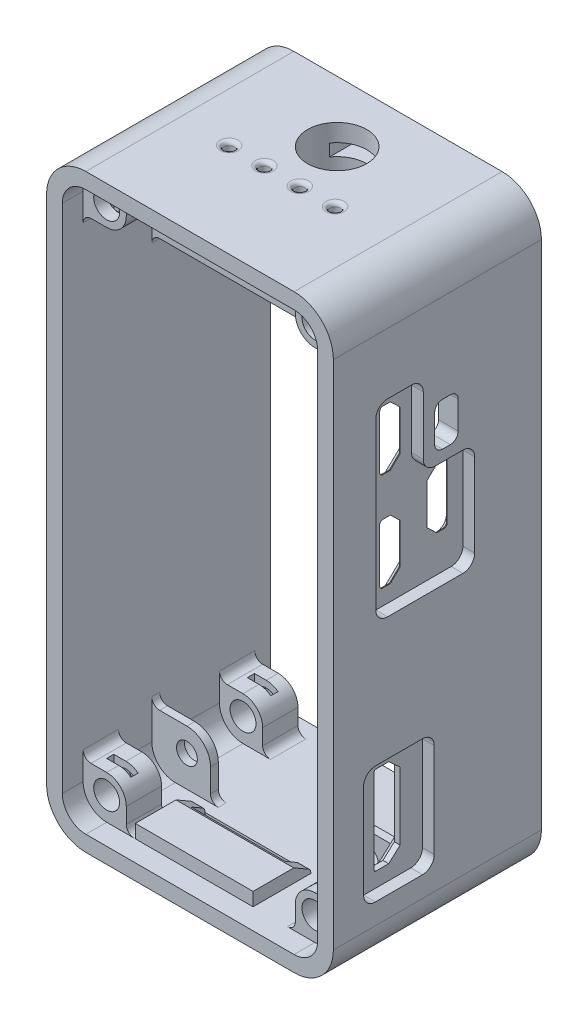
SolidWorks part; units mm, degrees
ref_plane "Front Plane" through (0, 0, 0) normal (0, 0, 1) x (1, 0, 0)
ref_plane "Top Plane" through (0, 0, 0) normal (0, 1, 0) x (1, 0, 0)
ref_plane "Right Plane" through (0, 0, 0) normal (1, 0, 0) x (0, 0, -1)
ref_plane "Plane1" through (15.42, 0, 0) normal (1, 0, 0) x (0, 0, -1)
ref_plane "Plane2" through (-16, 0, 0) normal (-1, 0, 0) x (0, 0, 1)
ref_plane "Plane3" through (0, 0, 12.35) normal (0, 0, -1) x (-1, 0, 0)
ref_plane "Plane4" through (0, 38.12, 0) normal (0, 1, 0) x (1, 0, 0)
ref_plane "Plane5" through (0, 0, -19.1) normal (0, 0, -1) x (-1, 0, 0)
ref_plane "Plane6" through (16.53, 0, 0) normal (1, 0, 0) x (0, 0, -1)
ref_plane "Plane7" through (0, -35, 0) normal (0, -1, 0) x (-1, 0, 0)
ref_axis "Axis1" through (16.53, -35, -39.8418) along (0, 0, 1)
ref_axis "Axis2" through (16.53, 38.12, 31.0702) along (0, 0, -1)
ref_axis "Axis3" through (16.53, 41.9436, 12.35) along (0, -1, 0)
ref_axis "Axis4" through (16.53, 40.8595, -19.1) along (0, -1, 0)
sketch "Sketch1" plane through (16.53, 0, 0) normal (1, 0, 0) x (0, 0, -1)
  line L0 (-31.0702, 38.12) -> (38.474, 38.12) construction
  line L1 (-12.35, 38.12) -> (19.1, 38.12)
  line L2 (-12.35, 38.12) -> (-12.35, -35)
  line L3 (-12.35, -35) -> (19.1, -35)
  line L4 (19.1, 38.12) -> (19.1, -35)
  line L6 (19.1, 40.8595) -> (19.1, -42.4423) construction
  line L7 (39.8418, -35) -> (-39.6201, -35) construction
  line L8 (-12.35, 41.9436) -> (-12.35, -39.5671) construction
extrude "Boss-Extrude1" add sketch "Sketch1" along normal blind 2
sketch "Sketch3" plane through (-16, 0, 0) normal (-1, 0, 0) x (0, 0, 1)
  line L4 (12.35, -35) -> (12.35, 38.12)
  line L5 (12.35, 38.12) -> (-19.1, 38.12)
  line L6 (-19.1, 38.12) -> (-19.1, -35)
  line L7 (-19.1, -35) -> (12.35, -35)
  line L8 (12.35, -35) -> (12.35, 38.12)
  line L9 (12.35, 38.12) -> (-19.1, 38.12)
  line L10 (-19.1, 38.12) -> (-19.1, -35)
  line L11 (-19.1, -35) -> (12.35, -35)
  dimension "D1" = 0
extrude "Boss-Extrude2" add sketch "Sketch3" along normal blind 2 separate body
sketch "Sketch4" plane through (0, 38.12, 0) normal (0, 1, 0) x (1, 0, 0)
  line L1 (-18, -12.35) -> (18.53, -12.35)
  line L2 (-18, -12.35) -> (-18, 19.1)
  line L3 (-18, 19.1) -> (18.53, 19.1)
  line L4 (18.53, -12.35) -> (18.53, 19.1)
extrude "Boss-Extrude3" add sketch "Sketch4" along normal blind 2
sketch "Sketch5" plane through (0, -35, 0) normal (0, -1, 0) x (1, 0, 0)
  line L1 (-18, 12.35) -> (18.53, 12.35)
  line L2 (-18, 12.35) -> (-18, -19.1)
  line L3 (-18, -19.1) -> (18.53, -19.1)
  line L4 (18.53, 12.35) -> (18.53, -19.1)
extrude "Boss-Extrude4" add sketch "Sketch5" against normal blind 2
fillet "Fillet1" radius 3 4 edges at (16.53, -33, -3.375) (16.53, 38.12, -3.375) (-16, 38.12, -3.375) (-16, -33, -3.375)
fillet "Fillet2" radius 5 4 edges at (-18, -35, -3.375) (18.53, -35, -3.375) (-18, 40.12, -3.375) (18.53, 40.12, -3.375)
sketch "Sketch6" plane through (18.53, 0, 0) normal (1, 0, 0) x (0, 0, -1)
  line L0 (-3.0523, 25.35) -> (-3.6, 25.35) construction
  line L3 (-2.3598, 18.0786) -> (-1.7075, 18.7048) construction
  line L4 (-3.6, 17.8) -> (-3.0523, 17.8) construction
  line L5 (-4, 24.95) -> (-4, 18.2) construction
  line L6 (-4, 24.95) -> (-4, 18.2)
  line L7 (-3.6, 17.8) -> (-2.65, 17.8)
  line L8 (-2.65, 17.8) -> (-1.4, 19)
  line L11 (-2.65, 25.35) -> (-3.6, 25.35)
  line L12 (-3.6, 5.3) -> (-3.0523, 5.3) construction
  line L13 (-2.3598, 5.5786) -> (-1.7075, 6.2048) construction
  line L14 (-1.4, 6.9262) -> (-1.4, 11.2238) construction
  line L15 (-1.7075, 11.9452) -> (-2.3598, 12.5714) construction
  line L16 (-3.0523, 12.85) -> (-3.6, 12.85) construction
  line L17 (-4, 12.45) -> (-4, 5.7) construction
  line L18 (-3.6, 5.3) -> (-2.65, 5.3)
  line L19 (-2.65, 5.3) -> (-1.4, 6.5)
  line L20 (-1.4, 6.5) -> (-1.4, 11.65)
  line L21 (-1.4, 11.65) -> (-2.65, 12.85)
  line L22 (-2.65, 12.85) -> (-3.6, 12.85)
  line L23 (-4, 12.45) -> (-4, 5.7)
  line L24 (4.2, 15.5) -> (3.6523, 15.5) construction
  line L25 (4.6, 8.35) -> (4.6, 15.1) construction
  line L26 (3.6523, 7.95) -> (4.2, 7.95) construction
  line L27 (2.3075, 8.8548) -> (2.9598, 8.2286) construction
  line L28 (2, 23.3) -> (2, 18.8)
  line L29 (2, 18.8) -> (4, 18.8)
  line L30 (4, 18.8) -> (4, 23.3)
  line L31 (4, 23.3) -> (2, 23.3)
  line L32 (2, 23.3) -> (2, 18.8) construction
  line L33 (2, 18.8) -> (4, 18.8) construction
  line L34 (4, 18.8) -> (4, 23.3) construction
  line L35 (4, 23.3) -> (2, 23.3) construction
  line L36 (2.5, 20.1) -> (3.5, 20.1)
  line L37 (3.5, 20.1) -> (3.5, 22)
  line L38 (3.5, 22) -> (2.5, 22)
  line L39 (2.5, 22) -> (2.5, 20.1)
  line L40 (2.5, 20.1) -> (3.5, 20.1) construction
  line L41 (3.5, 20.1) -> (3.5, 22) construction
  line L42 (3.5, 22) -> (2.5, 22) construction
  line L43 (2.5, 22) -> (2.5, 20.1) construction
  line L44 (2, 13.8738) -> (2, 9.5762) construction
  line L45 (2.9598, 15.2214) -> (2.3075, 14.5952) construction
  line L46 (4.2, 15.5) -> (3.25, 15.5)
  line L47 (4.6, 8.35) -> (4.6, 15.1)
  line L48 (3.25, 7.95) -> (4.2, 7.95)
  line L49 (2, 9.15) -> (3.25, 7.95)
  line L50 (2, 14.3) -> (2, 9.15)
  line L51 (3.25, 15.5) -> (2, 14.3)
  line L52 (-4.7, -14.45) -> (-4.7, -25.3) construction
  line L53 (-4.5, -25.5) -> (-2.9276, -25.5) construction
  line L54 (-2.7927, -25.4476) -> (-1.4651, -24.2345) construction
  line L55 (-2.9276, -14.25) -> (-4.5, -14.25) construction
  line L56 (-1.4651, -15.5155) -> (-2.7927, -14.3024) construction
  line L57 (-1.4, -24.0868) -> (-1.4, -15.6632) construction
  line L58 (-2.85, -14.25) -> (-4.5, -14.25)
  line L59 (-1.4, -15.575) -> (-2.85, -14.25)
  line L60 (-1.4, -24.175) -> (-1.4, -15.575)
  line L61 (-2.85, -25.5) -> (-1.4, -24.175)
  line L62 (-4.5, -25.5) -> (-2.85, -25.5)
  line L63 (-4.7, -14.45) -> (-4.7, -25.3)
  line L64 (-1.4, 24.15) -> (-2.65, 25.35)
  line L65 (-1.4, 19) -> (-1.4, 24.15)
  line L66 (1.5, 22.8) -> (1.5, 19.3)
  line L67 (2.5, 18.3) -> (3.5, 18.3)
  line L68 (4.5, 19.3) -> (4.5, 22.8)
  line L69 (3.5, 23.8) -> (2.5, 23.8)
  line L70 (1.5, 23.8) -> (1.5, 18.3) construction
  line L71 (1.5, 18.3) -> (4.5, 18.3) construction
  line L72 (4.5, 18.3) -> (4.5, 23.8) construction
  line L73 (4.5, 23.8) -> (1.5, 23.8) construction
  arc A0 (-4, 18.2) -> (-3.6, 17.8) centre (-3.6, 18.2) ccw construction
  arc A1 (-3.6, 25.35) -> (-4, 24.95) centre (-3.6, 24.95) ccw construction
  arc A6 (-4, 18.2) -> (-3.6, 17.8) centre (-3.6, 18.2) ccw
  arc A11 (-3.6, 25.35) -> (-4, 24.95) centre (-3.6, 24.95) ccw
  arc A12 (-4, 5.7) -> (-3.6, 5.3) centre (-3.6, 5.7) ccw construction
  arc A17 (-3.6, 12.85) -> (-4, 12.45) centre (-3.6, 12.45) ccw construction
  arc A18 (-4, 5.7) -> (-3.6, 5.3) centre (-3.6, 5.7) ccw
  arc A23 (-3.6, 12.85) -> (-4, 12.45) centre (-3.6, 12.45) ccw
  arc A25 (4.6, 15.1) -> (4.2, 15.5) centre (4.2, 15.1) ccw construction
  arc A26 (4.2, 7.95) -> (4.6, 8.35) centre (4.2, 8.35) ccw construction
  arc A31 (4.6, 15.1) -> (4.2, 15.5) centre (4.2, 15.1) ccw
  arc A32 (4.2, 7.95) -> (4.6, 8.35) centre (4.2, 8.35) ccw
  arc A37 (-4.7, -25.3) -> (-4.5, -25.5) centre (-4.5, -25.3) ccw construction
  arc A38 (-4.5, -14.25) -> (-4.7, -14.45) centre (-4.5, -14.45) ccw construction
  arc A42 (-4.5, -14.25) -> (-4.7, -14.45) centre (-4.5, -14.45) ccw
  arc A47 (-4.7, -25.3) -> (-4.5, -25.5) centre (-4.5, -25.3) ccw
  arc A48 (1.5, 19.3) -> (2.5, 18.3) centre (2.5, 19.3) ccw
  arc A49 (3.5, 18.3) -> (4.5, 19.3) centre (3.5, 19.3) ccw
  arc A50 (4.5, 22.8) -> (3.5, 23.8) centre (3.5, 22.8) ccw
  arc A51 (1.5, 22.8) -> (2.5, 23.8) centre (2.5, 22.8) cw
  dimension "D4" = 1
  dimension "D1" = 0
  dimension "D2" = 0
  dimension "D3" = 0.5
extrude "Cut-Extrude1" cut sketch "Sketch6" against normal blind 4
sketch "Sketch7" plane through (18.53, 0, 0) normal (1, 0, 0) x (0, 0, -1)
  line L0 (3.3166, 18.3) -> (3.3166, 15.5) construction
  line L1 (2.5, 18.3) -> (3.5, 18.3) construction
  line L2 (4.2, 15.5) -> (3.25, 15.5) construction
  line L3 (-1.4, 21.575) -> (1.5, 21.575) construction
  line L4 (-1.4, 19) -> (-1.4, 24.15) construction
  line L5 (1.5, 22.8) -> (1.5, 19.3) construction
  line L6 (0.05, 25.85) -> (0.05, 18.4)
  line L7 (1.55, 16.9) -> (5.1, 16.9)
  line L8 (-6, 25.85) -> (-6, 4.8)
  line L9 (-4, 24.95) -> (-4, 18.2) construction
  line L10 (-4.5, 27.35) -> (-1.45, 27.35)
  line L11 (-2.65, 25.35) -> (-3.6, 25.35) construction
  line L12 (-4.5, 3.3) -> (5.1, 3.3)
  line L13 (6.6, 4.8) -> (6.6, 15.4)
  line L14 (-3.6, 5.3) -> (-2.65, 5.3) construction
  line L15 (4.6, 8.35) -> (4.6, 15.1) construction
  line L16 (-4.7, -19.875) -> (-1.4, -19.875) construction
  line L17 (-6.05, -12.375) -> (-0.05, -12.375)
  line L18 (-7.55, -13.875) -> (-7.55, -25.875)
  line L19 (-6.05, -27.375) -> (-0.05, -27.375)
  line L20 (1.45, -13.875) -> (1.45, -25.875)
  line L21 (-4.7, -14.45) -> (-4.7, -25.3) construction
  line L22 (-1.4, -24.175) -> (-1.4, -15.575) construction
  line L23 (-3.05, -12.375) -> (-3.05, -27.375) construction
  arc A0 (-6, 4.8) -> (-4.5, 3.3) centre (-4.5, 4.8) ccw
  arc A1 (5.1, 3.3) -> (6.6, 4.8) centre (5.1, 4.8) ccw
  arc A2 (5.1, 16.9) -> (6.6, 15.4) centre (5.1, 15.4) cw
  arc A3 (1.55, 16.9) -> (0.05, 18.4) centre (1.55, 18.4) cw
  arc A4 (0.05, 25.85) -> (-1.45, 27.35) centre (-1.45, 25.85) ccw
  arc A5 (-6, 25.85) -> (-4.5, 27.35) centre (-4.5, 25.85) cw
  arc A6 (-0.05, -27.375) -> (1.45, -25.875) centre (-0.05, -25.875) ccw
  arc A7 (-0.05, -12.375) -> (1.45, -13.875) centre (-0.05, -13.875) cw
  arc A8 (-6.05, -12.375) -> (-7.55, -13.875) centre (-6.05, -13.875) ccw
  arc A9 (-7.55, -25.875) -> (-6.05, -27.375) centre (-6.05, -25.875) ccw
  point P14 (0.05, 21.575)
  point P17 (3.3166, 16.9)
  point P50 (-7.55, -19.875)
  point P53 (-3.05, -19.875)
  point P54 (-3.05, -19.875)
  dimension "D5" = 1.5
  dimension "D8" = 1.5
  dimension "D1" = 2
  dimension "D2" = 2
  dimension "D3" = 2
  dimension "D4" = 2
  dimension "D6" = 9
  dimension "D7" = 15
extrude "Cut-Extrude2" cut sketch "Sketch7" against normal blind 1.5
sketch "Sketch8" plane through (16.53, 0, 0) normal (-1, 0, 0) x (0, 0, 1)
  line L0 (7.2, 4.8) -> (7.2, 25.85)
  line L1 (4.5, 28.55) -> (1.45, 28.55)
  line L4 (-7.8, 15.4) -> (-7.8, 25.85)
  line L5 (-5.1, 28.55) -> (1.45, 28.55)
  line L6 (-5.1, 3.3) -> (4.5, 3.3)
  line L7 (-6.6, 15.4) -> (-6.6, 4.8)
  line L8 (-1.55, 16.9) -> (-5.1, 16.9)
  line L9 (-0.05, 25.85) -> (-0.05, 18.4)
  line L10 (4.5, 27.35) -> (1.45, 27.35)
  line L11 (6, 4.8) -> (6, 25.85)
  line L12 (-5.1, 3.3) -> (4.5, 3.3) construction
  line L13 (-6.6, 15.4) -> (-6.6, 4.8) construction
  line L14 (-1.55, 16.9) -> (-5.1, 16.9) construction
  line L15 (-0.05, 25.85) -> (-0.05, 18.4) construction
  line L16 (4.5, 27.35) -> (1.45, 27.35) construction
  line L17 (6, 4.8) -> (6, 25.85) construction
  line L18 (-2.5, 18.3) -> (-3.5, 18.3) construction
  line L19 (-1.5, 22.8) -> (-1.5, 19.3) construction
  line L24 (-7.8, 15.4) -> (-7.8, 4.8)
  line L25 (-5.1, 2.1) -> (4.5, 2.1)
  line L42 (2.65, 25.35) -> (1.4, 24.15) construction
  line L43 (3.6, 25.35) -> (2.65, 25.35) construction
  line L44 (4, 18.2) -> (4, 24.95) construction
  line L45 (2.65, 17.8) -> (3.6, 17.8) construction
  line L46 (1.4, 19) -> (2.65, 17.8) construction
  line L47 (1.4, 24.15) -> (1.4, 19) construction
  line L48 (2.65, 25.35) -> (1.4, 24.15)
  line L49 (3.6, 25.35) -> (2.65, 25.35)
  line L50 (4, 18.2) -> (4, 24.95)
  line L51 (2.65, 17.8) -> (3.6, 17.8)
  line L52 (1.4, 19) -> (2.65, 17.8)
  line L53 (1.4, 24.15) -> (1.4, 19)
  line L54 (1.4, 11.65) -> (1.4, 6.5) construction
  line L55 (1.4, 6.5) -> (2.65, 5.3) construction
  line L56 (2.65, 5.3) -> (3.6, 5.3) construction
  line L57 (4, 5.7) -> (4, 12.45) construction
  line L58 (2.65, 12.85) -> (1.4, 11.65) construction
  line L59 (3.6, 12.85) -> (2.65, 12.85) construction
  line L60 (1.4, 11.65) -> (1.4, 6.5)
  line L61 (1.4, 6.5) -> (2.65, 5.3)
  line L62 (2.65, 5.3) -> (3.6, 5.3)
  line L63 (4, 5.7) -> (4, 12.45)
  line L64 (2.65, 12.85) -> (1.4, 11.65)
  line L65 (3.6, 12.85) -> (2.65, 12.85)
  line L66 (-4.2, 7.95) -> (-3.25, 7.95) construction
  line L67 (-4.6, 15.1) -> (-4.6, 8.35) construction
  line L68 (-3.25, 15.5) -> (-4.2, 15.5) construction
  line L69 (-2, 14.3) -> (-3.25, 15.5) construction
  line L70 (-2, 9.15) -> (-2, 14.3) construction
  line L71 (-3.25, 7.95) -> (-2, 9.15) construction
  line L72 (-4.2, 7.95) -> (-3.25, 7.95)
  line L73 (-4.6, 15.1) -> (-4.6, 8.35)
  line L74 (-3.25, 15.5) -> (-4.2, 15.5)
  line L75 (-2, 14.3) -> (-3.25, 15.5)
  line L76 (-2, 9.15) -> (-2, 14.3)
  line L77 (-3.25, 7.95) -> (-2, 9.15)
  line L78 (-3.5, 23.8) -> (-2.5, 23.8) construction
  line L79 (-4.5, 19.3) -> (-4.5, 22.8) construction
  line L80 (-2.5, 18.3) -> (-3.5, 18.3)
  line L81 (-1.5, 22.8) -> (-1.5, 19.3)
  line L82 (-3.5, 23.8) -> (-2.5, 23.8)
  line L83 (-4.5, 19.3) -> (-4.5, 22.8)
  line L88 (-1.25, 25.85) -> (-1.25, 18.4) construction
  line L89 (-1.55, 18.1) -> (-5.1, 18.1) construction
  arc A0 (4.5, 2.1) -> (7.2, 4.8) centre (4.5, 4.8) ccw
  arc A1 (7.2, 25.85) -> (4.5, 28.55) centre (4.5, 25.85) ccw
  arc A4 (-7.8, 25.85) -> (-5.1, 28.55) centre (-5.1, 25.85) cw
  arc A5 (-4.5, 19.3) -> (-3.5, 18.3) centre (-3.5, 19.3) ccw construction
  arc A6 (4.5, 3.3) -> (6, 4.8) centre (4.5, 4.8) ccw
  arc A7 (-6.6, 4.8) -> (-5.1, 3.3) centre (-5.1, 4.8) ccw
  arc A8 (-5.1, 16.9) -> (-6.6, 15.4) centre (-5.1, 15.4) ccw
  arc A9 (-1.55, 16.9) -> (-0.05, 18.4) centre (-1.55, 18.4) ccw
  arc A10 (1.45, 27.35) -> (-0.05, 25.85) centre (1.45, 25.85) ccw
  arc A11 (6, 25.85) -> (4.5, 27.35) centre (4.5, 25.85) ccw
  arc A12 (4.5, 3.3) -> (6, 4.8) centre (4.5, 4.8) ccw construction
  arc A13 (-6.6, 4.8) -> (-5.1, 3.3) centre (-5.1, 4.8) ccw construction
  arc A14 (-5.1, 16.9) -> (-6.6, 15.4) centre (-5.1, 15.4) ccw construction
  arc A15 (-1.55, 16.9) -> (-0.05, 18.4) centre (-1.55, 18.4) ccw construction
  arc A16 (1.45, 27.35) -> (-0.05, 25.85) centre (1.45, 25.85) ccw construction
  arc A17 (6, 25.85) -> (4.5, 27.35) centre (4.5, 25.85) ccw construction
  arc A18 (-2.5, 18.3) -> (-1.5, 19.3) centre (-2.5, 19.3) ccw construction
  arc A19 (-1.5, 22.8) -> (-2.5, 23.8) centre (-2.5, 22.8) ccw construction
  arc A25 (-7.8, 4.8) -> (-5.1, 2.1) centre (-5.1, 4.8) ccw
  arc A34 (4, 24.95) -> (3.6, 25.35) centre (3.6, 24.95) ccw construction
  arc A35 (3.6, 17.8) -> (4, 18.2) centre (3.6, 18.2) ccw construction
  arc A36 (4, 24.95) -> (3.6, 25.35) centre (3.6, 24.95) ccw
  arc A37 (3.6, 17.8) -> (4, 18.2) centre (3.6, 18.2) ccw
  arc A38 (3.6, 5.3) -> (4, 5.7) centre (3.6, 5.7) ccw construction
  arc A39 (4, 12.45) -> (3.6, 12.85) centre (3.6, 12.45) ccw construction
  arc A40 (3.6, 5.3) -> (4, 5.7) centre (3.6, 5.7) ccw
  arc A41 (4, 12.45) -> (3.6, 12.85) centre (3.6, 12.45) ccw
  arc A42 (-4.6, 8.35) -> (-4.2, 7.95) centre (-4.2, 8.35) ccw construction
  arc A43 (-4.2, 15.5) -> (-4.6, 15.1) centre (-4.2, 15.1) ccw construction
  arc A44 (-4.6, 8.35) -> (-4.2, 7.95) centre (-4.2, 8.35) ccw
  arc A45 (-4.2, 15.5) -> (-4.6, 15.1) centre (-4.2, 15.1) ccw
  arc A46 (-3.5, 23.8) -> (-4.5, 22.8) centre (-3.5, 22.8) ccw construction
  arc A47 (-4.5, 19.3) -> (-3.5, 18.3) centre (-3.5, 19.3) ccw
  arc A48 (-2.5, 18.3) -> (-1.5, 19.3) centre (-2.5, 19.3) ccw
  arc A49 (-1.5, 22.8) -> (-2.5, 23.8) centre (-2.5, 22.8) ccw
  arc A50 (-3.5, 23.8) -> (-4.5, 22.8) centre (-3.5, 22.8) ccw
  arc A56 (1.45, 28.55) -> (-1.25, 25.85) centre (1.45, 25.85) ccw construction
  arc A57 (-1.55, 18.1) -> (-1.25, 18.4) centre (-1.55, 18.4) ccw construction
  arc A58 (-5.1, 18.1) -> (-7.8, 15.4) centre (-5.1, 15.4) ccw construction
  dimension "D2" = 2.7
  dimension "D1" = 0
  dimension "D3" = 1.2
extrude "Boss-Extrude5" add sketch "Sketch8" along normal blind 0.5
sketch "Sketch9" plane through (16.53, 0, 0) normal (-1, 0, 0) x (0, 0, 1)
  line L0 (0.05, -28.575) -> (6.05, -28.575)
  line L1 (8.75, -25.875) -> (8.75, -13.875)
  line L2 (6.05, -11.175) -> (0.05, -11.175)
  line L3 (-2.65, -13.875) -> (-2.65, -25.875)
  line L4 (-1.45, -13.875) -> (-1.45, -25.875)
  line L5 (6.05, -12.375) -> (0.05, -12.375)
  line L6 (7.55, -25.875) -> (7.55, -13.875)
  line L7 (0.05, -27.375) -> (6.05, -27.375)
  line L8 (-1.45, -13.875) -> (-1.45, -25.875) construction
  line L9 (6.05, -12.375) -> (0.05, -12.375) construction
  line L10 (7.55, -25.875) -> (7.55, -13.875) construction
  line L11 (0.05, -27.375) -> (6.05, -27.375) construction
  line L12 (1.4, -24.175) -> (2.85, -25.5) construction
  line L13 (2.85, -25.5) -> (4.5, -25.5) construction
  line L14 (1.4, -15.575) -> (1.4, -24.175) construction
  line L15 (2.85, -14.25) -> (1.4, -15.575) construction
  line L16 (4.5, -14.25) -> (2.85, -14.25) construction
  line L17 (4.7, -25.3) -> (4.7, -14.45) construction
  line L18 (1.4, -24.175) -> (2.85, -25.5)
  line L19 (2.85, -25.5) -> (4.5, -25.5)
  line L20 (1.4, -15.575) -> (1.4, -24.175)
  line L21 (2.85, -14.25) -> (1.4, -15.575)
  line L22 (4.5, -14.25) -> (2.85, -14.25)
  line L23 (4.7, -25.3) -> (4.7, -14.45)
  line L24 (8.75, -25.875) -> (8.75, -28.575)
  line L25 (8.75, -28.575) -> (6.05, -28.575)
  arc A0 (-2.65, -25.875) -> (0.05, -28.575) centre (0.05, -25.875) ccw
  arc A1 (6.05, -28.575) -> (8.75, -25.875) centre (6.05, -25.875) ccw construction
  arc A2 (8.75, -13.875) -> (6.05, -11.175) centre (6.05, -13.875) ccw
  arc A3 (0.05, -11.175) -> (-2.65, -13.875) centre (0.05, -13.875) ccw
  arc A4 (-1.45, -25.875) -> (0.05, -27.375) centre (0.05, -25.875) ccw
  arc A5 (0.05, -12.375) -> (-1.45, -13.875) centre (0.05, -13.875) ccw
  arc A6 (7.55, -13.875) -> (6.05, -12.375) centre (6.05, -13.875) ccw
  arc A7 (6.05, -27.375) -> (7.55, -25.875) centre (6.05, -25.875) ccw
  arc A8 (-1.45, -25.875) -> (0.05, -27.375) centre (0.05, -25.875) ccw construction
  arc A9 (0.05, -12.375) -> (-1.45, -13.875) centre (0.05, -13.875) ccw construction
  arc A10 (7.55, -13.875) -> (6.05, -12.375) centre (6.05, -13.875) ccw construction
  arc A11 (6.05, -27.375) -> (7.55, -25.875) centre (6.05, -25.875) ccw construction
  arc A12 (4.5, -25.5) -> (4.7, -25.3) centre (4.5, -25.3) ccw construction
  arc A13 (4.7, -14.45) -> (4.5, -14.25) centre (4.5, -14.45) ccw construction
  arc A14 (4.5, -25.5) -> (4.7, -25.3) centre (4.5, -25.3) ccw
  arc A15 (4.7, -14.45) -> (4.5, -14.25) centre (4.5, -14.45) ccw
  dimension "D1" = 0
  dimension "D2" = 1.2
extrude "Boss-Extrude6" add sketch "Sketch9" along normal up to surface (1.13 mm away)
chamfer "Chamfer1" distance 0.9 angle 45 32 edges at (16.03, 12.25, 2.025) (16.03, 5.9, 2.025) (16.03, 9.075, 1.4) (16.03, 24.75, 2.025) (16.03, 18.4, 2.025) (16.03, 21.575, 1.4) (16.03, 8.55, -2.625) (16.03, 14.9, -2.625) (16.03, 11.725, -2) (16.03, 15.5, -3.725) (16.03, 7.95, -3.725) (16.03, 15.3828, -4.4828) (16.03, 8.0672, -4.4828) (16.03, 11.725, -4.6) (16.03, 5.3, 3.125) (16.03, 12.85, 3.125) (16.03, 5.4172, 3.8828) (16.03, 12.7328, 3.8828) (16.03, 9.075, 4) (16.03, 17.8, 3.125) (16.03, 25.35, 3.125) (16.03, 17.9172, 3.8828) (16.03, 25.2328, 3.8828) (16.03, 21.575, 4) (15.4, -14.9125, 2.125) (15.4, -19.875, 1.4) (15.4, -24.8375, 2.125) (15.4, -25.5, 3.675) (15.4, -14.25, 3.675) (15.4, -25.4414, 4.6414) (15.4, -14.3086, 4.6414) (15.4, -19.875, 4.7)
sketch "Sketch10" plane through (0, -35, 0) normal (0, -1, 0) x (1, 0, 0)
  line L0 (4.15, 2.75) -> (4.15, 1.4) construction
  line L1 (1.65, 2.85) -> (4.05, 2.85) construction
  line L2 (4.15, 1.4) -> (1.65, 1.4) construction
  line L3 (1.65, 1.4) -> (1.65, 2.85) construction
  line L4 (-7.85, 1.4) -> (-7.85, 2.75) construction
  line L5 (-7.75, 2.85) -> (-6.75, 2.85) construction
  line L6 (-6.75, 2.85) -> (-6.75, 1.4) construction
  line L7 (-6.75, 1.4) -> (-7.85, 1.4) construction
  line L8 (1.65, 2.85) -> (4.05, 2.85) construction
  line L9 (4.15, 2.75) -> (4.15, 1.4) construction
  line L10 (4.15, 1.4) -> (1.65, 1.4) construction
  line L11 (1.65, 1.4) -> (1.65, 2.85) construction
  line L12 (-7.85, 1.4) -> (-7.85, 2.75) construction
  line L13 (-7.75, 2.85) -> (-6.75, 2.85) construction
  line L14 (-6.75, 2.85) -> (-6.75, 1.4) construction
  line L15 (-6.75, 1.4) -> (-7.85, 1.4) construction
  line L17 (4.15, 1.4) -> (-7.85, 1.4)
  line L18 (4.15, 1.4) -> (4.15, 3.1408)
  line L19 (4.15, 3.1408) -> (-7.85, 3.1408)
  line L20 (-7.85, 1.4) -> (-7.85, 3.1408)
  arc A0 (4.15, 2.75) -> (4.05, 2.85) centre (4.05, 2.75) ccw construction
  arc A1 (-7.75, 2.85) -> (-7.85, 2.75) centre (-7.75, 2.75) ccw construction
  arc A2 (4.15, 2.75) -> (4.05, 2.85) centre (4.05, 2.75) ccw construction
  arc A3 (-7.75, 2.85) -> (-7.85, 2.75) centre (-7.75, 2.75) ccw construction
extrude "Cut-Extrude3" cut sketch "Sketch10" against normal blind 3
sketch "Sketch11" plane through (0, -33, 0) normal (0, 1, 0) x (1, 0, 0)
  line L0 (-7.85, -1.4) -> (4.15, -1.4) construction
  line L1 (5.65, -7.1408) -> (-9.35, -7.1408)
  line L2 (5.65, -7.1408) -> (5.65, -1.4)
  line L3 (5.65, -1.4) -> (4.15, -1.4)
  line L4 (-9.35, -7.1408) -> (-9.35, -1.4)
  line L5 (4.15, -1.4) -> (4.15, -3.1408) construction
  line L6 (-7.85, -3.1408) -> (-7.85, -1.4) construction
  line L7 (4.15, -3.1408) -> (-7.85, -3.1408) construction
  line L8 (4.15, -1.4) -> (4.15, -3.1408) construction
  line L9 (4.15, -3.1408) -> (-7.85, -3.1408) construction
  line L10 (-7.85, -3.1408) -> (-7.85, -1.4) construction
  line L11 (4.15, -1.4) -> (4.15, -3.1408)
  line L12 (4.15, -3.1408) -> (-7.85, -3.1408)
  line L13 (-7.85, -3.1408) -> (-7.85, -1.4)
  line L14 (-7.85, -1.4) -> (-9.35, -1.4)
  dimension "D1" = 1.5
  dimension "D2" = 1.5
  dimension "D3" = 4
extrude "Boss-Extrude7" add sketch "Sketch11" along normal blind 1.7
sketch "Sketch12" plane through (0, 0, 3.1408) normal (0, 0, -1) x (-1, 0, 0)
  line L0 (-4.15, -35) -> (7.85, -35) construction
  line L1 (-4.15, -35) -> (7.85, -35) construction
  line L2 (9.4089, -39.5975) -> (-5.7089, -39.5975)
  arc A0 (9.4089, -39.5975) -> (-5.7089, -39.5975) centre (1.85, -39.5975) ccw
revolve "Cut-Revolve1" cut sketch "Sketch12" angle 90 about L2
fillet "Fillet4" radius 0.5 1 edges at (-1.85, -32.0386, 3.1408)
sketch "Sketch14" plane through (0, 40.12, 0) normal (0, 1, 0) x (1, 0, 0)
  line L0 (7.4, 1) -> (6.1, 1) construction
  line L1 (6.1, 1) -> (6.1, 0.8) construction
  line L2 (6.1, 0.8) -> (7.4, 0.8) construction
  line L3 (7.4, 0.8) -> (7.4, 1) construction
  line L4 (7.4, 0.8) -> (6.1, 0.8) construction
  line L5 (6.1, 0.8) -> (6.1, 0.2) construction
  line L6 (6.1, 0.2) -> (7.4, 0.2) construction
  line L7 (7.4, 0.2) -> (7.4, 0.8) construction
  line L8 (7.4, 1) -> (6.1, 1) construction
  line L9 (6.1, 1) -> (6.1, 0.8) construction
  line L10 (6.1, 0.8) -> (7.4, 0.8) construction
  line L11 (7.4, 0.8) -> (7.4, 1) construction
  line L12 (7.4, 0.8) -> (6.1, 0.8) construction
  line L13 (6.1, 0.8) -> (6.1, 0.2) construction
  line L14 (6.1, 0.2) -> (7.4, 0.2) construction
  line L15 (7.4, 0.2) -> (7.4, 0.8) construction
  line L16 (2.9, 1) -> (1.6, 1) construction
  line L17 (1.6, 1) -> (1.6, 0.8) construction
  line L18 (1.6, 0.8) -> (2.9, 0.8) construction
  line L19 (2.9, 0.8) -> (2.9, 1) construction
  line L20 (2.9, 0.8) -> (1.6, 0.8) construction
  line L21 (1.6, 0.8) -> (1.6, 0.2) construction
  line L22 (1.6, 0.2) -> (2.9, 0.2) construction
  line L23 (2.9, 0.2) -> (2.9, 0.8) construction
  line L24 (2.9, 1) -> (1.6, 1) construction
  line L25 (1.6, 1) -> (1.6, 0.8) construction
  line L26 (1.6, 0.8) -> (2.9, 0.8) construction
  line L27 (2.9, 0.8) -> (2.9, 1) construction
  line L28 (2.9, 0.8) -> (1.6, 0.8) construction
  line L29 (1.6, 0.8) -> (1.6, 0.2) construction
  line L30 (1.6, 0.2) -> (2.9, 0.2) construction
  line L31 (2.9, 0.2) -> (2.9, 0.8) construction
  line L32 (-1.6, 1) -> (-2.9, 1) construction
  line L33 (-2.9, 1) -> (-2.9, 0.8) construction
  line L34 (-2.9, 0.8) -> (-1.6, 0.8) construction
  line L35 (-1.6, 0.8) -> (-1.6, 1) construction
  line L36 (-1.6, 0.8) -> (-2.9, 0.8) construction
  line L37 (-2.9, 0.8) -> (-2.9, 0.2) construction
  line L38 (-2.9, 0.2) -> (-1.6, 0.2) construction
  line L39 (-1.6, 0.2) -> (-1.6, 0.8) construction
  line L40 (-1.6, 1) -> (-2.9, 1) construction
  line L41 (-2.9, 1) -> (-2.9, 0.8) construction
  line L42 (-2.9, 0.8) -> (-1.6, 0.8) construction
  line L43 (-1.6, 0.8) -> (-1.6, 1) construction
  line L44 (-1.6, 0.8) -> (-2.9, 0.8) construction
  line L45 (-2.9, 0.8) -> (-2.9, 0.2) construction
  line L46 (-2.9, 0.2) -> (-1.6, 0.2) construction
  line L47 (-1.6, 0.2) -> (-1.6, 0.8) construction
  line L48 (-6.1, 1) -> (-7.4, 1) construction
  line L49 (-7.4, 1) -> (-7.4, 0.8) construction
  line L50 (-7.4, 0.8) -> (-6.1, 0.8) construction
  line L51 (-6.1, 0.8) -> (-6.1, 1) construction
  line L52 (-6.1, 0.8) -> (-7.4, 0.8) construction
  line L53 (-7.4, 0.8) -> (-7.4, 0.2) construction
  line L54 (-7.4, 0.2) -> (-6.1, 0.2) construction
  line L55 (-6.1, 0.2) -> (-6.1, 0.8) construction
  line L56 (-6.1, 1) -> (-7.4, 1) construction
  line L57 (-7.4, 1) -> (-7.4, 0.8) construction
  line L58 (-7.4, 0.8) -> (-6.1, 0.8) construction
  line L59 (-6.1, 0.8) -> (-6.1, 1) construction
  line L60 (-6.1, 0.8) -> (-7.4, 0.8) construction
  line L61 (-7.4, 0.8) -> (-7.4, 0.2) construction
  line L62 (-7.4, 0.2) -> (-6.1, 0.2) construction
  line L63 (-6.1, 0.2) -> (-6.1, 0.8) construction
  line L64 (6.75, 1) -> (6.75, 0.2) construction
  line L65 (2.25, 1) -> (2.25, 0.2) construction
  line L66 (-2.25, 1) -> (-2.25, 0.2) construction
  line L67 (-6.75, 1) -> (-6.75, 0.2) construction
  circle A0 centre (6.75, 0.6) radius 0.65
  circle A1 centre (2.25, 0.6) radius 0.65
  circle A2 centre (-2.25, 0.6) radius 0.65
  circle A3 centre (-6.75, 0.6) radius 0.65
  point P48 (6.75, -0.05)
extrude "Cut-Extrude4" cut sketch "Sketch14" against normal up to next
fillet "Fillet5" radius 0.5 4 edges at (-6.75, 40.12, 0.05) (-2.25, 40.12, 0.05) (2.25, 40.12, 0.05) (6.75, 40.12, 0.05)
sketch "Sketch15" plane through (0, 0, 0) normal (0, 0, -1) x (-1, 0, 0)
  line L0 (-13.53, 38.12) -> (13, 38.12) construction
  line L1 (16, 35.12) -> (16, -30) construction
  line L2 (-16.53, -30) -> (-16.53, 35.12) construction
  line L3 (13, -33) -> (-13.53, -33) construction
  line L4 (15, -28.75) -> (15, 28.75)
  line L5 (11.25, 32.5) -> (-11.25, 32.5)
  line L6 (-15, 28.75) -> (-15, -28.75)
  line L7 (-11.25, -32.5) -> (11.25, -32.5)
  line L8 (15, -28.75) -> (15, 28.75) construction
  line L9 (11.25, 32.5) -> (-11.25, 32.5) construction
  line L10 (-15, 28.75) -> (-15, -28.75) construction
  line L11 (-11.25, -32.5) -> (11.25, -32.5) construction
  line L12 (13, -33) -> (-13.53, -33)
  line L13 (-16.53, -30) -> (-16.53, 35.12)
  line L14 (16, 35.12) -> (16, -30)
  line L15 (-13.53, 38.12) -> (13, 38.12)
  circle A0 centre (11.525, 29.025) radius 1.325 construction
  circle A1 centre (11.525, 29.025) radius 1.325
  circle A2 centre (-11.525, 29.025) radius 1.325 construction
  circle A3 centre (-11.525, 29.025) radius 1.325
  arc A4 (11.25, -32.5) -> (15, -28.75) centre (11.25, -28.75) ccw
  arc A5 (15, 28.75) -> (11.25, 32.5) centre (11.25, 28.75) ccw
  arc A6 (-11.25, 32.5) -> (-15, 28.75) centre (-11.25, 28.75) ccw
  arc A7 (-15, -28.75) -> (-11.25, -32.5) centre (-11.25, -28.75) ccw
  arc A8 (11.25, -32.5) -> (15, -28.75) centre (11.25, -28.75) ccw construction
  arc A9 (15, 28.75) -> (11.25, 32.5) centre (11.25, 28.75) ccw construction
  arc A10 (-11.25, 32.5) -> (-15, 28.75) centre (-11.25, 28.75) ccw construction
  arc A11 (-15, -28.75) -> (-11.25, -32.5) centre (-11.25, -28.75) ccw construction
  circle A12 centre (-11.525, -29.025) radius 1.325 construction
  circle A13 centre (-11.525, -29.025) radius 1.325
  circle A14 centre (11.525, -29.025) radius 1.325 construction
  circle A15 centre (11.525, -29.025) radius 1.325
  arc A16 (-13.53, 38.12) -> (-16.53, 35.12) centre (-13.53, 35.12) ccw construction
  arc A17 (16, 35.12) -> (13, 38.12) centre (13, 35.12) ccw construction
  arc A18 (13, -33) -> (16, -30) centre (13, -30) ccw construction
  arc A19 (-16.53, -30) -> (-13.53, -33) centre (-13.53, -30) ccw construction
  arc A20 (13, -33) -> (16, -30) centre (13, -30) ccw
  arc A21 (-16.53, -30) -> (-13.53, -33) centre (-13.53, -30) ccw
  arc A22 (-13.53, 38.12) -> (-16.53, 35.12) centre (-13.53, 35.12) ccw
  arc A23 (16, 35.12) -> (13, 38.12) centre (13, 35.12) ccw
  dimension "D1" = 0
sketch "Sketch16" plane through (0, 0, 0) normal (0, 0, -1) x (-1, 0, 0)
  line L0 (-13.53, 38.12) -> (13, 38.12) construction
  line L1 (-16.53, -30) -> (-16.53, 35.12) construction
  line L2 (13, -33) -> (-13.53, -33) construction
  line L3 (16, 35.12) -> (16, -30) construction
  line L4 (-13.53, 38.12) -> (13, 38.12)
  line L5 (-16.53, -30) -> (-16.53, -26.025)
  line L6 (13, -33) -> (8.525, -33)
  line L7 (16, 35.12) -> (16, 26.025)
  line L8 (-8.525, -29.025) -> (-8.525, -33)
  line L9 (-11.525, -26.025) -> (-16.53, -26.025)
  line L10 (11.525, -26.025) -> (16, -26.025)
  line L11 (8.525, -29.025) -> (8.525, -33)
  line L12 (-16.53, 26.025) -> (16, 26.025)
  line L13 (-16.53, 26.025) -> (-16.53, 35.12)
  line L14 (16, -26.025) -> (16, -30)
  line L15 (-8.525, -33) -> (-13.53, -33)
  arc A0 (16, 35.12) -> (13, 38.12) centre (13, 35.12) ccw construction
  arc A1 (-13.53, 38.12) -> (-16.53, 35.12) centre (-13.53, 35.12) ccw construction
  arc A2 (-16.53, -30) -> (-13.53, -33) centre (-13.53, -30) ccw construction
  arc A3 (13, -33) -> (16, -30) centre (13, -30) ccw construction
  arc A4 (16, 35.12) -> (13, 38.12) centre (13, 35.12) ccw
  arc A5 (-13.53, 38.12) -> (-16.53, 35.12) centre (-13.53, 35.12) ccw
  arc A6 (-16.53, -30) -> (-13.53, -33) centre (-13.53, -30) ccw
  arc A7 (13, -33) -> (16, -30) centre (13, -30) ccw
  circle A8 centre (-11.525, 29.025) radius 1.325 construction
  circle A9 centre (-11.525, 29.025) radius 1.325
  circle A10 centre (11.525, 29.025) radius 1.325 construction
  circle A11 centre (11.525, 29.025) radius 1.325
  circle A12 centre (11.525, -29.025) radius 1.325 construction
  circle A13 centre (11.525, -29.025) radius 1.325
  circle A14 centre (-11.525, -29.025) radius 1.325 construction
  circle A15 centre (-11.525, -29.025) radius 1.325
  circle A16 centre (-11.525, -29.025) radius 3 construction
  circle A17 centre (11.525, -29.025) radius 3 construction
  circle A18 centre (-11.525, 29.025) radius 3 construction
  circle A19 centre (11.525, 29.025) radius 3 construction
  arc A20 (-8.525, -29.025) -> (-11.525, -26.025) centre (-11.525, -29.025) ccw
  arc A21 (11.525, -26.025) -> (8.525, -29.025) centre (11.525, -29.025) ccw
  circle A22 centre (-11.525, 29.025) radius 3 construction
  circle A23 centre (11.525, 29.025) radius 3 construction
extrude "Boss-Extrude8" add sketch "Sketch16" along normal blind 1
sketch "Sketch17" plane through (0, 0, 0) normal (0, 0, 1) x (1, 0, 0)
  line L0 (-11.25, 32.5) -> (11.25, 32.5) construction
  line L1 (-11.25, 32.5) -> (11.25, 32.5) construction
  line L2 (16.53, 32.7) -> (-16, 32.7)
  line L3 (16.53, -30) -> (16.53, 35.12) construction
  line L4 (-16, 35.12) -> (-16, -30) construction
  line L5 (13.53, 38.12) -> (-13, 38.12) construction
  line L6 (13.53, 38.12) -> (-13, 38.12)
  line L7 (-16, 35.12) -> (-16, 32.7)
  line L8 (16.53, 35.12) -> (16.53, 32.7)
  arc A0 (-13, 38.12) -> (-16, 35.12) centre (-13, 35.12) ccw construction
  arc A1 (16.53, 35.12) -> (13.53, 38.12) centre (13.53, 35.12) ccw construction
  arc A2 (-13, 38.12) -> (-16, 35.12) centre (-13, 35.12) ccw
  arc A3 (16.53, 35.12) -> (13.53, 38.12) centre (13.53, 35.12) ccw
  dimension "D1" = 0.2
extrude "Boss-Extrude9" add sketch "Sketch17" along normal blind 0.7
sketch "Sketch18" plane through (0, 0, -1) normal (0, 0, -1) x (-1, 0, 0)
  line L0 (7.4, 28.5) -> (6.1, 28.5) construction
  line L1 (2.9, 28.5) -> (1.6, 28.5) construction
  line L2 (-1.6, 28.5) -> (-2.9, 28.5) construction
  line L3 (-6.1, 28.5) -> (-7.4, 28.5) construction
  line L4 (7.4, 28.5) -> (6.1, 28.5)
  line L5 (2.9, 28.5) -> (1.6, 28.5)
  line L6 (-1.6, 28.5) -> (-2.9, 28.5)
  line L7 (-6.1, 28.5) -> (-7.4, 28.5)
  line L8 (-2.7623, 38.12) -> (-6.2377, 38.12) construction
  line L9 (-7.4, 28) -> (-6.1, 28)
  line L10 (-7.4, 28) -> (-7.4, 38.12)
  line L11 (-7.4, 38.12) -> (-6.1, 38.12)
  line L12 (-6.1, 28) -> (-6.1, 38.12)
  line L13 (1.7377, 38.12) -> (-1.7377, 38.12) construction
  line L14 (-2.9, 28) -> (-1.6, 28)
  line L15 (-2.9, 28) -> (-2.9, 38.12)
  line L16 (-2.9, 38.12) -> (-1.6, 38.12)
  line L17 (-1.6, 28) -> (-1.6, 38.12)
  line L18 (6.2377, 38.12) -> (2.7623, 38.12) construction
  line L19 (1.6, 28) -> (2.9, 28)
  line L20 (1.6, 28) -> (1.6, 38.12)
  line L21 (1.6, 38.12) -> (2.9, 38.12)
  line L22 (2.9, 28) -> (2.9, 38.12)
  line L23 (13, 38.12) -> (7.2623, 38.12) construction
  line L24 (6.1, 28) -> (7.4, 28)
  line L25 (6.1, 28) -> (6.1, 38.12)
  line L26 (6.1, 38.12) -> (7.4, 38.12)
  line L27 (7.4, 28) -> (7.4, 38.12)
  line L28 (-6.75, 28.5) -> (-6.75, 28) construction
  line L29 (-2.25, 28.5) -> (-2.25, 28) construction
  line L30 (2.25, 28.5) -> (2.25, 28) construction
  line L31 (6.75, 28.5) -> (6.75, 28) construction
  line L32 (-6.1, 38.12) -> (-7.4, 38.12) construction
  line L33 (-6.1, 38.12) -> (-7.4, 38.12)
  dimension "D1" = 0.5
extrude "Cut-Extrude5" cut sketch "Sketch18" against normal up to vertex (1.05 mm away) contours L9 L12 L10 | L14 L17 L15 | L19 L22 L20 | L24 L27 L25 region at (6.75, 33.31, -1) region at (2.25, 33.31, -1) region at (-2.25, 33.31, -1) region at (-6.75, 33.31, -1) up to point (6.75, 40.12, 0.05)
fillet "Fillet6" radius 1 6 edges at (-16, -26.025, -0.5) (-16, 26.025, -0.5) (8.525, -33, -0.5) (15.4, -26.025, -0.5) (16.03, 26.025, -0.5) (-8.525, -33, -0.5)
sketch "Sketch19" plane through (0, 40.12, 0) normal (0, 1, 0) x (1, 0, 0)
  circle A0 centre (0.265, 7.3487) radius 3.7709
sketch "Sketch20" plane through (0, 38.12, 0) normal (0, -1, 0) x (1, 0, 0)
  circle A0 centre (0.265, -7.3487) radius 3.7709 construction
  circle A1 centre (0.265, -7.3487) radius 3.7709 construction
  circle A2 centre (0.265, -7.3487) radius 5.7709
  point P5 (0.265, -13.1197)
  point P8 (0.265, -7.3487)
  dimension "D1" = 2
sketch "Sketch21" plane through (0, 0, -1) normal (0, 0, -1) x (-1, 0, 0)
  line L4 (-16.53, 35.12) -> (-16.53, 32.7)
  line L5 (13, 38.12) -> (-13.53, 38.12)
  line L6 (16, 32.7) -> (16, 35.12)
  line L7 (-16.53, 32.7) -> (16, 32.7)
  line L8 (-16.53, 35.12) -> (-16.53, 32.7)
  line L9 (13, 38.12) -> (-13.53, 38.12)
  line L10 (16, 32.7) -> (16, 35.12)
  line L11 (-16.53, 32.7) -> (16, 32.7)
  arc A2 (-13.53, 38.12) -> (-16.53, 35.12) centre (-13.53, 35.12) ccw
  arc A3 (16, 35.12) -> (13, 38.12) centre (13, 35.12) ccw
  arc A4 (-13.53, 38.12) -> (-16.53, 35.12) centre (-13.53, 35.12) ccw
  arc A5 (16, 35.12) -> (13, 38.12) centre (13, 35.12) ccw
  dimension "D1" = 0
extrude "Boss-Extrude10" add sketch "Sketch21" along normal up to vertex (12.1197 mm away) up to point (0.265, 38.12, -13.1197)
extrude "Cut-Extrude6" cut sketch "Sketch19" against normal up to next
chamfer "Chamfer2" distance 0.5 angle 45 1 edges at (0.265, 32.7, -3.5778)
sketch "Sketch22" plane through (0, 0, -13.1197) normal (0, 0, -1) x (-1, 0, 0)
  line L0 (3.385, 35.64) -> (-3.915, 35.64) construction
  line L1 (-3.915, 38.6) -> (3.385, 38.6) construction
  line L2 (3.385, 35.64) -> (-3.915, 35.64) construction
  line L3 (-3.915, 38.6) -> (3.385, 38.6) construction
  line L4 (-0.265, 35.64) -> (-0.265, 38.6) construction
  line L6 (-3.3769, 36.3493) -> (2.8469, 36.3493)
  line L7 (-3.3769, 36.3493) -> (-3.3769, 37.8907)
  line L8 (-3.3769, 37.8907) -> (2.8469, 37.8907)
  line L9 (2.8469, 36.3493) -> (2.8469, 37.8907)
  line L10 (-3.3769, 36.3493) -> (2.8469, 37.8907) construction
  line L11 (-3.3769, 37.8907) -> (2.8469, 36.3493) construction
  point P6 (-0.265, 37.12)
extrude "Cut-Extrude7" cut sketch "Sketch22" against normal up to vertex (5.7709 mm away) up to point (0.265, 38.12, -7.3487)
sketch "Sketch23" plane through (0, 32.7, 0) normal (0, -1, 0) x (1, 0, 0)
  line L1 (7.4, -1) -> (6.1, -1)
  line L2 (7.4, -1) -> (7.4, -1.25)
  line L3 (7.4, -1.25) -> (6.1, -1.25)
  line L4 (6.1, -1) -> (6.1, -1.25)
  line L5 (2.9, -1) -> (1.6, -1)
  line L6 (2.9, -1) -> (2.9, -1.25)
  line L7 (2.9, -1.25) -> (1.6, -1.25)
  line L8 (1.6, -1) -> (1.6, -1.25)
  line L9 (-1.6, -1) -> (-2.9, -1)
  line L10 (-1.6, -1) -> (-1.6, -1.25)
  line L11 (-1.6, -1.25) -> (-2.9, -1.25)
  line L12 (-2.9, -1) -> (-2.9, -1.25)
  line L13 (-6.1, -1) -> (-7.4, -1)
  line L14 (-6.1, -1) -> (-6.1, -1.25)
  line L15 (-6.1, -1.25) -> (-7.4, -1.25)
  line L16 (-7.4, -1) -> (-7.4, -1.25)
  circle A0 centre (6.75, -0.6) radius 0.65 construction
  circle A1 centre (6.75, -0.6) radius 0.65 construction
  circle A2 centre (2.25, -0.6) radius 0.65 construction
  circle A3 centre (2.25, -0.6) radius 0.65 construction
  circle A4 centre (-2.25, -0.6) radius 0.65 construction
  circle A5 centre (-2.25, -0.6) radius 0.65 construction
  circle A6 centre (-6.75, -0.6) radius 0.65 construction
  circle A7 centre (-6.75, -0.6) radius 0.65 construction
extrude "Cut-Extrude8" cut sketch "Sketch23" against normal up to surface (5.42 mm away) up to face at (0.265, 38.12, 6.525)
sketch "Sketch24" plane through (0, 0, -19.1) normal (0, 0, -1) x (-1, 0, 0)
  line L4 (-13.53, -35) -> (13, -35)
  line L5 (18, -30) -> (18, 35.12)
  line L6 (13, 40.12) -> (-13.53, 40.12)
  line L7 (-18.53, 35.12) -> (-18.53, -30)
  line L8 (-13.53, -35) -> (13, -35)
  line L9 (18, -30) -> (18, 35.12)
  line L10 (13, 40.12) -> (-13.53, 40.12)
  line L11 (-18.53, 35.12) -> (-18.53, -30)
  arc A4 (13, -35) -> (18, -30) centre (13, -30) ccw
  arc A5 (18, 35.12) -> (13, 40.12) centre (13, 35.12) ccw
  arc A6 (-13.53, 40.12) -> (-18.53, 35.12) centre (-13.53, 35.12) ccw
  arc A7 (-18.53, -30) -> (-13.53, -35) centre (-13.53, -30) ccw
  arc A8 (13, -35) -> (18, -30) centre (13, -30) ccw
  arc A9 (18, 35.12) -> (13, 40.12) centre (13, 35.12) ccw
  arc A10 (-13.53, 40.12) -> (-18.53, 35.12) centre (-13.53, 35.12) ccw
  arc A11 (-18.53, -30) -> (-13.53, -35) centre (-13.53, -30) ccw
  dimension "D1" = 0
extrude "Cut-Extrude9" cut sketch "Sketch24" against normal up to surface (4 mm away)
sketch "Sketch25" plane through (0, 0, -13.1197) normal (0, 0, -1) x (-1, 0, 0)
  line L0 (16, 35.12) -> (16, -30) construction
  line L1 (13, 32.62) -> (16, 32.62)
  line L2 (16, 35.12) -> (16, 32.62)
  line L4 (16, -27.5) -> (16, -30)
  line L5 (-16.53, -27.5) -> (-13.53, -27.5)
  line L6 (-11.03, 38.12) -> (-13.53, 38.12)
  line L9 (-11.03, 38.12) -> (-11.03, 35.12)
  line L10 (10.5, 35.12) -> (10.5, 38.12)
  line L13 (-16.53, 32.62) -> (-13.53, 32.62)
  line L15 (-11.03, -33) -> (-11.03, -30)
  line L16 (10.5, -30) -> (10.5, -33)
  line L18 (13, -27.5) -> (16, -27.5)
  line L20 (13, -33) -> (-13.53, -33) construction
  line L21 (13, -33) -> (10.5, -33)
  line L22 (-16.53, -30) -> (-16.53, 35.12) construction
  line L23 (-16.53, -30) -> (-16.53, -27.5)
  line L24 (13, 38.12) -> (-13.53, 38.12) construction
  line L25 (13, 38.12) -> (10.5, 38.12)
  line L26 (-16.53, 32.62) -> (-16.53, 35.12)
  line L27 (-11.03, -33) -> (-13.53, -33)
  arc A2 (-13.53, 32.62) -> (-11.03, 35.12) centre (-13.53, 35.12) ccw
  arc A7 (-11.03, -30) -> (-13.53, -27.5) centre (-13.53, -30) ccw
  arc A10 (13, -27.5) -> (10.5, -30) centre (13, -30) ccw
  arc A15 (10.5, 35.12) -> (13, 32.62) centre (13, 35.12) ccw
  arc A16 (16, 35.12) -> (13, 38.12) centre (13, 35.12) ccw construction
  arc A17 (16, 35.12) -> (13, 38.12) centre (13, 35.12) ccw
  arc A18 (-13.53, 38.12) -> (-16.53, 35.12) centre (-13.53, 35.12) ccw construction
  arc A19 (-13.53, 38.12) -> (-16.53, 35.12) centre (-13.53, 35.12) ccw
  arc A20 (13, -33) -> (16, -30) centre (13, -30) ccw construction
  arc A21 (13, -33) -> (16, -30) centre (13, -30) ccw
  arc A22 (-16.53, -30) -> (-13.53, -33) centre (-13.53, -30) ccw construction
  arc A23 (-16.53, -30) -> (-13.53, -33) centre (-13.53, -30) ccw
  dimension "D1" = 2.5
extrude "Boss-Extrude11" add sketch "Sketch25" against normal blind 4.5
fillet "Fillet7" radius 1 6 edges at (-16, -27.5, -10.8697) (-10.5, -33, -10.8697) (11.03, -33, -10.8697) (16.53, -27.5, -10.8697) (-16, 32.62, -10.8697) (16.53, 32.62, -10.8697)
sketch "Sketch26" plane through (0, 0, -13.1197) normal (0, 0, -1) x (-1, 0, 0)
  line L0 (-13.53, 35.12) -> (13, 35.12) construction
  line L1 (13, 35.12) -> (13, -30) construction
  circle A0 centre (13, 35.12) radius 1.65
  circle A1 centre (-13.53, 35.12) radius 1.65
  circle A2 centre (13, -30) radius 1.65
  circle A3 centre (-13.53, -30) radius 1.65
  point P12 (13, -30)
  dimension "D1" = 3.3
extrude "Cut-Extrude10" cut sketch "Sketch26" against normal up to surface (4.5 mm away) up to face at (13.5322, -30.0022, -8.6197)
sketch "Sketch27" plane through (0, 0, -8.6197) normal (0, 0, -1) x (-1, 0, 0)
  circle A0 centre (13, 35.12) radius 1.05 construction
  circle A1 centre (13, 35.12) radius 1.05 construction
  circle A2 centre (-13.53, 35.12) radius 1.05 construction
  circle A3 centre (-13.53, 35.12) radius 1.05 construction
  circle A4 centre (13, 35.12) radius 1.25
  circle A5 centre (-13.53, 35.12) radius 1.25
  point P7 (13, 35.12)
  dimension "D1" = 0.2
extrude "Cut-Extrude11" cut sketch "Sketch27" against normal up to surface (9.3197 mm away) up to face at (0.265, 35.5204, 0.7)
sketch "Sketch28" plane through (0, 32.62, 0) normal (0, -1, 0) x (1, 0, 0)
  line L0 (-14.5, -10.1197) -> (-11.5, -10.1197) construction
  line L1 (-11.5, -12.1197) -> (-14.5, -12.1197) construction
  line L2 (-14.5, -10.1197) -> (-11.5, -10.1197) construction
  line L3 (-11.5, -12.1197) -> (-14.5, -12.1197) construction
  line L4 (15.03, -12.1197) -> (12.03, -12.1197) construction
  line L5 (12.03, -10.1197) -> (15.03, -10.1197) construction
  line L6 (15.03, -12.1197) -> (12.03, -12.1197) construction
  line L7 (12.03, -10.1197) -> (15.03, -10.1197) construction
  line L8 (-13, -12.1197) -> (-13, -10.1197) construction
  line L9 (13.53, -12.1197) -> (13.53, -10.1197) construction
  line L10 (-11.5, -10.6606) -> (-14.5, -10.6606)
  line L11 (-11.5, -10.6606) -> (-11.5, -11.5787)
  line L12 (-11.5, -11.5787) -> (-14.5, -11.5787)
  line L13 (-14.5, -10.6606) -> (-14.5, -11.5787)
  line L14 (-11.5, -10.6606) -> (-14.5, -11.5787) construction
  line L15 (-11.5, -11.5787) -> (-14.5, -10.6606) construction
  line L17 (15.03, -10.6606) -> (12.03, -10.6606)
  line L18 (15.03, -10.6606) -> (15.03, -11.5787)
  line L19 (15.03, -11.5787) -> (12.03, -11.5787)
  line L20 (12.03, -10.6606) -> (12.03, -11.5787)
  line L21 (15.03, -10.6606) -> (12.03, -11.5787) construction
  line L22 (15.03, -11.5787) -> (12.03, -10.6606) construction
  point P10 (-13, -11.1197)
  point P17 (13.53, -11.1197)
extrude "Cut-Extrude12" cut sketch "Sketch28" against normal up to vertex (2.5 mm away) up to point (-13, 35.12, -8.6197)
sketch "Sketch29" plane through (0, -27.5, 0) normal (0, 1, 0) x (1, 0, 0)
  line L0 (-11.5, 10.6606) -> (-11.5, 11.5787) construction
  line L1 (-11.5, 11.5787) -> (-14.5, 11.5787) construction
  line L2 (-11.5, 10.6606) -> (-14.5, 10.6606) construction
  line L3 (-14.5, 10.6606) -> (-14.5, 11.5787) construction
  line L4 (-11.5, 10.6606) -> (-11.5, 11.5787)
  line L5 (-11.5, 11.5787) -> (-14.5, 11.5787)
  line L6 (-11.5, 10.6606) -> (-14.5, 10.6606)
  line L7 (-14.5, 10.6606) -> (-14.5, 11.5787)
  line L8 (12.03, 10.6606) -> (12.03, 11.5787) construction
  line L9 (15.03, 11.5787) -> (12.03, 11.5787) construction
  line L10 (15.03, 10.6606) -> (12.03, 10.6606) construction
  line L11 (15.03, 10.6606) -> (15.03, 11.5787) construction
  line L12 (12.03, 10.6606) -> (12.03, 11.5787)
  line L13 (15.03, 11.5787) -> (12.03, 11.5787)
  line L14 (15.03, 10.6606) -> (12.03, 10.6606)
  line L15 (15.03, 10.6606) -> (15.03, 11.5787)
extrude "Cut-Extrude13" cut sketch "Sketch29" against normal up to vertex (2.5 mm away) up to point (-13, -30, -13.1197)
sketch "Sketch30" plane through (0, 0, 12.35) normal (0, 0, 1) x (1, 0, 0)
  line L4 (-18, 35.12) -> (-18, -30)
  line L5 (-13, -35) -> (13.53, -35)
  line L6 (18.53, -30) -> (18.53, 35.12)
  line L7 (13.53, 40.12) -> (-13, 40.12)
  line L8 (-18, 35.12) -> (-18, -30)
  line L9 (-13, -35) -> (13.53, -35)
  line L10 (18.53, -30) -> (18.53, 35.12)
  line L11 (13.53, 40.12) -> (-13, 40.12)
  arc A4 (-18, -30) -> (-13, -35) centre (-13, -30) ccw
  arc A5 (13.53, -35) -> (18.53, -30) centre (13.53, -30) ccw
  arc A6 (18.53, 35.12) -> (13.53, 40.12) centre (13.53, 35.12) ccw
  arc A7 (-13, 40.12) -> (-18, 35.12) centre (-13, 35.12) ccw
  arc A8 (-18, -30) -> (-13, -35) centre (-13, -30) ccw
  arc A9 (13.53, -35) -> (18.53, -30) centre (13.53, -30) ccw
  arc A10 (18.53, 35.12) -> (13.53, 40.12) centre (13.53, 35.12) ccw
  arc A11 (-13, 40.12) -> (-18, 35.12) centre (-13, 35.12) ccw
  dimension "D1" = 0
extrude "Cut-Extrude16" cut sketch "Sketch30" against normal up to surface (0.95 mm away)
ref_plane "Plane8" through (0, 0, 8.75) normal (0, 0, -1) x (-1, 0, 0)
sketch "Sketch31" plane through (0, 0, 8.75) normal (0, 0, -1) x (-1, 0, 0)
  line L4 (-11.03, 35.12) -> (-11.03, 38.12)
  line L5 (-16.53, 32.62) -> (-13.53, 32.62)
  line L6 (-16.53, 35.12) -> (-16.53, 32.62)
  line L7 (-11.03, 38.12) -> (-13.53, 38.12)
  line L8 (-11.03, 35.12) -> (-11.03, 38.12)
  line L9 (-16.53, 32.62) -> (-13.53, 32.62)
  line L10 (-16.53, 35.12) -> (-16.53, 32.62)
  line L11 (-11.03, 38.12) -> (-13.53, 38.12)
  line L12 (-16.53, -27.5) -> (-16.53, -30)
  line L13 (-13.53, -33) -> (-11.03, -33)
  line L14 (-11.03, -33) -> (-11.03, -30)
  line L15 (-13.53, -27.5) -> (-16.53, -27.5)
  line L16 (-16.53, -27.5) -> (-16.53, -30)
  line L17 (-13.53, -33) -> (-11.03, -33)
  line L18 (-11.03, -33) -> (-11.03, -30)
  line L19 (-13.53, -27.5) -> (-16.53, -27.5)
  line L20 (13, 32.62) -> (16, 32.62)
  line L21 (16, 32.62) -> (16, 35.12)
  line L22 (13, 38.12) -> (10.5, 38.12)
  line L23 (10.5, 38.12) -> (10.5, 35.12)
  line L24 (13, 32.62) -> (16, 32.62)
  line L25 (16, 32.62) -> (16, 35.12)
  line L26 (13, 38.12) -> (10.5, 38.12)
  line L27 (10.5, 38.12) -> (10.5, 35.12)
  line L28 (10.5, -33) -> (13, -33)
  line L29 (16, -30) -> (16, -27.5)
  line L30 (16, -27.5) -> (13, -27.5)
  line L31 (10.5, -30) -> (10.5, -33)
  line L32 (10.5, -33) -> (13, -33)
  line L33 (16, -30) -> (16, -27.5)
  line L34 (16, -27.5) -> (13, -27.5)
  line L35 (10.5, -30) -> (10.5, -33)
  arc A2 (-13.53, 32.62) -> (-11.03, 35.12) centre (-13.53, 35.12) ccw
  arc A3 (-13.53, 38.12) -> (-16.53, 35.12) centre (-13.53, 35.12) ccw
  arc A4 (-13.53, 32.62) -> (-11.03, 35.12) centre (-13.53, 35.12) ccw
  arc A5 (-13.53, 38.12) -> (-16.53, 35.12) centre (-13.53, 35.12) ccw
  arc A6 (-16.53, -30) -> (-13.53, -33) centre (-13.53, -30) ccw
  arc A7 (-11.03, -30) -> (-13.53, -27.5) centre (-13.53, -30) ccw
  arc A8 (-16.53, -30) -> (-13.53, -33) centre (-13.53, -30) ccw
  arc A9 (-11.03, -30) -> (-13.53, -27.5) centre (-13.53, -30) ccw
  arc A10 (16, 35.12) -> (13, 38.12) centre (13, 35.12) ccw
  arc A11 (10.5, 35.12) -> (13, 32.62) centre (13, 35.12) ccw
  arc A12 (16, 35.12) -> (13, 38.12) centre (13, 35.12) ccw
  arc A13 (10.5, 35.12) -> (13, 32.62) centre (13, 35.12) ccw
  arc A14 (13, -33) -> (16, -30) centre (13, -30) ccw
  arc A15 (13, -27.5) -> (10.5, -30) centre (13, -30) ccw
  arc A16 (13, -33) -> (16, -30) centre (13, -30) ccw
  arc A17 (13, -27.5) -> (10.5, -30) centre (13, -30) ccw
  dimension "D1" = 0
  dimension "D2" = 0
  dimension "D3" = 0
  dimension "D4" = 0
extrude "Boss-Extrude12" add sketch "Sketch31" along normal blind 4.5
sketch "Sketch32" plane through (0, 0, 4.25) normal (0, 0, -1) x (-1, 0, 0)
  circle A1 centre (-13.53, -30) radius 1.65
  circle A2 centre (-13.53, -30) radius 1.65
  circle A3 centre (13, -30) radius 1.65
  circle A4 centre (13, -30) radius 1.65
  circle A5 centre (-13.53, 35.12) radius 1.65
  circle A6 centre (-13.53, 35.12) radius 1.65
  circle A7 centre (13, 35.12) radius 1.65
  circle A8 centre (13, 35.12) radius 1.65
  point P1 (13, -30)
  point P14 (13, 35.12)
  dimension "D1" = 0
  dimension "D2" = 0
  dimension "D3" = 0
  dimension "D4" = 0
extrude "Cut-Extrude17" cut sketch "Sketch32" against normal up to surface (4.5 mm away) up to face at (13.7139, 35.3039, 8.75)
fillet "Fillet8" radius 1 8 edges at (-16, 32.62, 6.5) (-10.5, 38.12, 6.5) (11.03, 38.12, 6.5) (16.53, 32.62, 6.5) (-16, -27.5, 6.5) (-10.5, -33, 6.5) (15.4, -27.5, 6.5) (11.03, -33, 6.5)
sketch "Sketch33" plane through (0, -27.5, 0) normal (0, 1, 0) x (1, 0, 0)
  line L0 (15.03, -7.75) -> (12.03, -7.75) construction
  line L1 (12.03, -5.75) -> (15.03, -5.75) construction
  line L2 (-14.5, -5.75) -> (-11.5, -5.75) construction
  line L3 (-11.5, -7.75) -> (-14.5, -7.75) construction
  line L4 (15.03, -7.75) -> (12.03, -7.75) construction
  line L5 (12.03, -5.75) -> (15.03, -5.75) construction
  line L6 (-14.5, -5.75) -> (-11.5, -5.75) construction
  line L7 (-11.5, -7.75) -> (-14.5, -7.75) construction
  line L8 (13.53, -7.75) -> (13.53, -5.75) construction
  line L9 (-13, -7.75) -> (-13, -5.75) construction
  line L10 (-11.5, 10.6606) -> (-11.5, 11.5787) construction
  line L11 (15.0766, -7.2091) -> (11.9834, -7.2091)
  line L12 (15.0766, -7.2091) -> (15.0766, -6.2909)
  line L13 (15.0766, -6.2909) -> (11.9834, -6.2909)
  line L14 (11.9834, -7.2091) -> (11.9834, -6.2909)
  line L15 (15.0766, -7.2091) -> (11.9834, -6.2909) construction
  line L16 (15.0766, -6.2909) -> (11.9834, -7.2091) construction
  line L17 (-11.4534, -7.2091) -> (-14.5466, -7.2091)
  line L18 (-11.4534, -7.2091) -> (-11.4534, -6.2909)
  line L19 (-11.4534, -6.2909) -> (-14.5466, -6.2909)
  line L20 (-14.5466, -7.2091) -> (-14.5466, -6.2909)
  line L21 (-11.4534, -7.2091) -> (-14.5466, -6.2909) construction
  line L22 (-11.4534, -6.2909) -> (-14.5466, -7.2091) construction
  point P12 (13.53, -6.75)
  point P17 (-13, -6.75)
extrude "Cut-Extrude18" cut sketch "Sketch33" against normal up to vertex (2.5 mm away) up to point (-13, -30, 4.25)
sketch "Sketch34" plane through (0, -27.5, 0) normal (0, -1, 0) x (1, 0, 0)
  line L4 (14.4, 7.2091) -> (14.4, 6.2909)
  line L5 (14.4, 6.2909) -> (15.0766, 6.2909)
  line L6 (15.0766, 6.2909) -> (15.0766, 7.2091)
  line L7 (15.0766, 7.2091) -> (14.4, 7.2091)
  line L8 (14.4, 7.2091) -> (14.4, 6.2909)
  line L9 (14.4, 6.2909) -> (15.0766, 6.2909)
  line L10 (15.0766, 6.2909) -> (15.0766, 7.2091)
  line L11 (15.0766, 7.2091) -> (14.4, 7.2091)
  dimension "D1" = 0
extrude "Cut-Extrude19" cut sketch "Sketch34" against normal up to next
sketch "Sketch35" plane through (0, 32.62, 0) normal (0, -1, 0) x (1, 0, 0)
  line L0 (-14.5466, 7.2091) -> (-14.5466, 6.2909) construction
  line L1 (-11.4534, 7.2091) -> (-14.5466, 7.2091) construction
  line L2 (-11.4534, 6.2909) -> (-14.5466, 6.2909) construction
  line L3 (-11.4534, 7.2091) -> (-11.4534, 6.2909) construction
  line L4 (11.9834, 7.2091) -> (11.9834, 6.2909) construction
  line L5 (15.0766, 7.2091) -> (11.9834, 7.2091) construction
  line L6 (15.0766, 6.2909) -> (11.9834, 6.2909) construction
  line L7 (15.0766, 7.2091) -> (15.0766, 6.2909) construction
  line L8 (-14.5466, 7.2091) -> (-14.5466, 6.2909)
  line L9 (-11.4534, 7.2091) -> (-14.5466, 7.2091)
  line L10 (-11.4534, 6.2909) -> (-14.5466, 6.2909)
  line L11 (-11.4534, 7.2091) -> (-11.4534, 6.2909)
  line L12 (11.9834, 7.2091) -> (11.9834, 6.2909)
  line L13 (15.0766, 7.2091) -> (11.9834, 7.2091)
  line L14 (15.0766, 6.2909) -> (11.9834, 6.2909)
  line L15 (15.0766, 7.2091) -> (15.0766, 6.2909)
extrude "Cut-Extrude20" cut sketch "Sketch35" against normal up to vertex (2.5 mm away) up to point (-13, 35.12, 4.25)
sketch "Sketch36" plane through (0, 32.7, 0) normal (0, -1, 0) x (1, 0, 0)
  line L0 (11.25, -2) -> (15, -2) construction
  line L1 (-11.25, -2) -> (11.25, -2) construction
  line L2 (11.25, -2) -> (15, -2) construction
  line L3 (-11.25, -2) -> (11.25, -2) construction
  line L4 (15.53, -8.6197) -> (13.53, -8.6197) construction
  line L5 (15, -8.6197) -> (6.1, -8.6197)
  line L6 (15, -8.6197) -> (15, -2)
  line L7 (15, -2) -> (6.1, -2)
  line L8 (6.1, -8.6197) -> (6.1, -2)
  line L9 (6.1, -1) -> (6.1, -1.25) construction
  line L10 (0.265, -7.3487) -> (0.265, -2) construction
  line L11 (-14.47, -2) -> (-5.57, -2)
  line L12 (-14.47, -8.6197) -> (-14.47, -2)
  line L13 (-5.57, -8.6197) -> (-5.57, -2)
  line L14 (-14.47, -8.6197) -> (-5.57, -8.6197)
extrude "Cut-Extrude21" cut sketch "Sketch36" against normal up to surface (5.42 mm away) up to face at (0.265, 38.12, 6.35)
sketch "Sketch37" plane through (0, 0, 7.1408) normal (0, 0, 1) x (1, 0, 0)
  line L4 (-9.35, -33) -> (5.65, -33)
  line L5 (5.65, -33) -> (5.65, -31.3)
  line L6 (5.65, -31.3) -> (-9.35, -31.3)
  line L7 (-9.35, -31.3) -> (-9.35, -33)
  line L8 (-9.35, -33) -> (5.65, -33)
  line L9 (5.65, -33) -> (5.65, -31.3)
  line L10 (5.65, -31.3) -> (-9.35, -31.3)
  line L11 (-9.35, -31.3) -> (-9.35, -33)
  dimension "D1" = 0
extrude "Boss-Extrude13" add sketch "Sketch37" along normal up to surface (1.6092 mm away) up to face at (-14.65, -30, 8.75)
chamfer "Chamfer3" distance 1.25 angle 60 1 edges at (-8.6, -31.3, 1.4) first distance on face at (-8.6, -32.15, 1.4)
fillet "Fillet9" radius 0.5 2 edges at (-8.6, -32.55, 1.4) (4.9, -32.55, 1.4)
